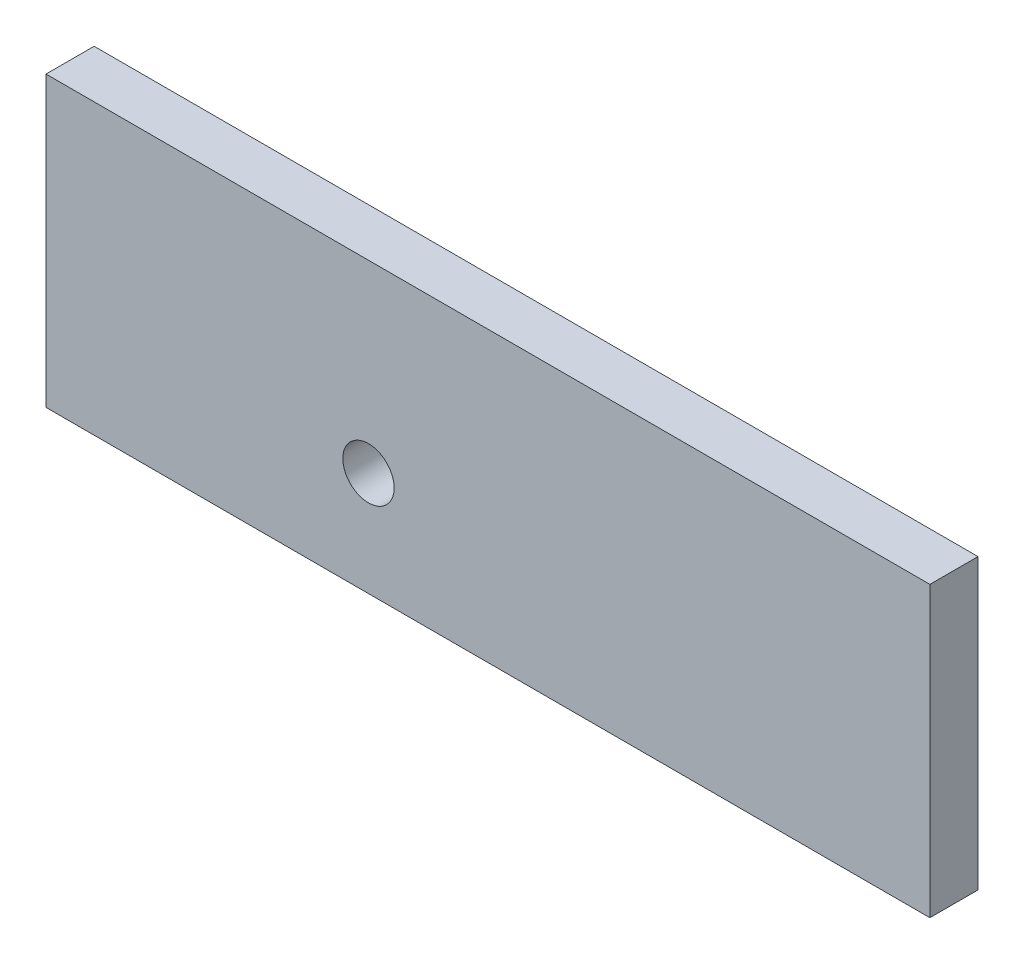
SolidWorks part; units mm, degrees
ref_plane "前视基准面" through (0, 0, 0) normal (0, 0, 1) x (1, 0, 0)
ref_plane "上视基准面" through (0, 0, 0) normal (0, 1, 0) x (1, 0, 0)
ref_plane "右视基准面" through (0, 0, 0) normal (1, 0, 0) x (0, 0, -1)
sketch "草图1" plane through (0, 0, 0) normal (0, 0, 1) x (1, 0, 0)
  line L0 (18.1, 0.8) -> (-9.4526, 0.8)
  line L2 (18.1, 9.8) -> (18.1, 0.8)
  line L3 (-9.4526, 0.8) -> (-9.4526, 9.8)
  line L5 (-9.4526, 9.8) -> (18.1, 9.8)
  circle A1 centre (0.6, 3.3) radius 1.75 construction
  circle A2 centre (0.6, 4.05) radius 1 construction
  dimension "D1" = 2
  dimension "D2" = 9
extrude "base" add sketch "草图1" along normal blind 1.5 contours L5 L2 L0 L3
sketch "草图4" plane through (0, 0, 0) normal (0, 0, -1) x (-1, 0, 0)
  circle A1 centre (-11.1, 3.3) radius 0.85 construction
  circle A3 centre (-0.6, 3.3) radius 1.75 construction
  circle A4 centre (-11.1, 3.3) radius 0.725
  dimension "D1" = 1.45
extrude "axis" add sketch "草图4" along normal offset from surface (1.9 mm away) 0.4 offset beyond the face yes
sketch "草图5" plane through (0, 0, 0) normal (0, 0, -1) x (-1, 0, 0)
  circle A1 centre (-0.6, 3.3) radius 1.75 construction
  circle A2 centre (-0.6, 4.05) radius 1 construction
  dimension "D1" = 2
hole_wizard "M2 螺纹孔的螺纹孔钻头1" positions "3D草图1" profile "草图6" hole size "M2" standard "ISO" end condition up to next
sketch3d "3D草图1"
  point P0 (0.6, 4.05, 0)
sketch "草图6" plane through (0.6, 4.05, 0) normal (1, 0, 0) x (0, 1, 0)
  line L0 (0, 0) -> (0, 1.5)
  line L1 (0, 1.5) -> (0.8, 1.5)
  line L2 (0.8, 1.5) -> (0.8, 0)
  line L5 (0.8, 0) -> (0, 0)
  line L11 (0, -6.35) -> (0, 107.95) construction
  dimension "通孔孔直径" = 1.6
  dimension "通孔孔深度" = 1.5
sketch "草图7" plane through (0, 0, 1.5) normal (0, 0, 1) x (1, 0, 0)
  line L0 (18.1, 9.8) -> (18.1, 0.8) construction
  circle A0 centre (15.1, 4.05) radius 1
  dimension "D1" = 2
  dimension "D2" = 3
sketch "Sketch1" plane through (0, 0, 1.5) normal (0, 0, 1) x (1, 0, 0)
  line L0 (-9.4526, 5.3) -> (18.1, 5.3) construction
  line L1 (-9.4526, 0.8) -> (-9.4526, 9.8) construction
  line L2 (18.1, 9.8) -> (18.1, 0.8) construction
  line L3 (-5.4526, 5.3) -> (-0.4526, 5.3)
  line L4 (8.1, 5.3) -> (13.1, 5.3)
  point P10 (13.003, 5.3)
  dimension "D1" = 5
  dimension "D2" = 4
  dimension "D3" = 5
